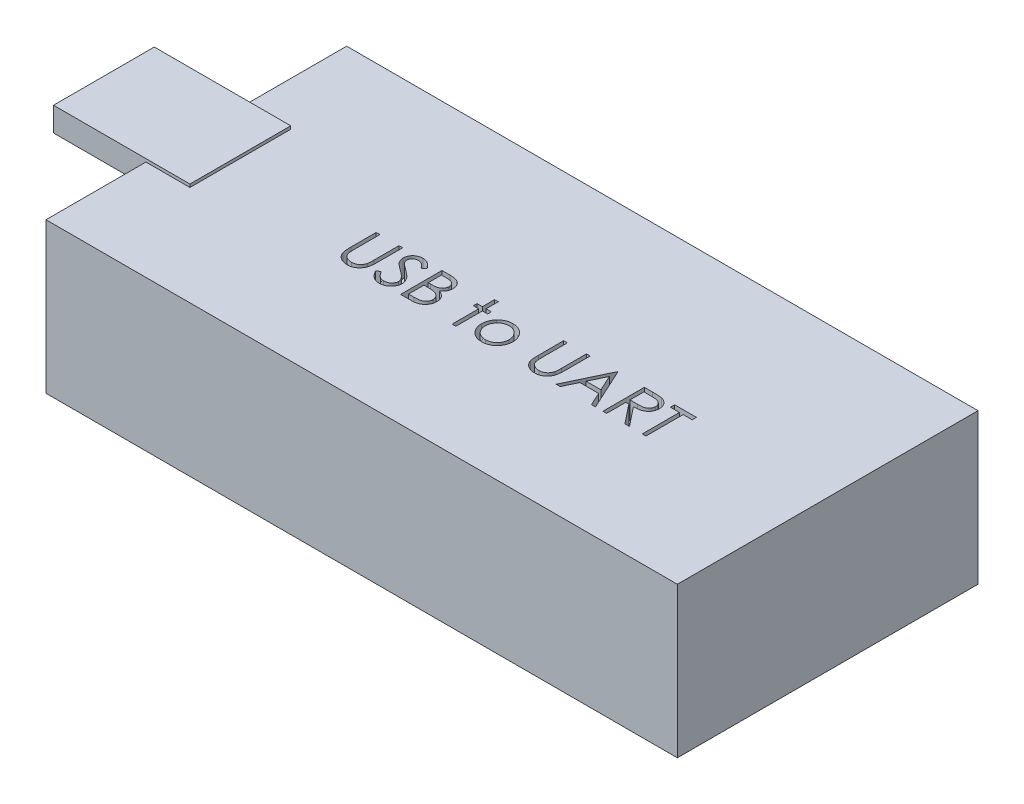
SolidWorks part; units mm, degrees
ref_plane "Front Plane" through (0, 0, 0) normal (0, 0, 1) x (1, 0, 0)
ref_plane "Top Plane" through (0, 0, 0) normal (0, 1, 0) x (1, 0, 0)
ref_plane "Right Plane" through (0, 0, 0) normal (1, 0, 0) x (0, 0, -1)
sketch "Sketch1" plane through (0, 0, 0) normal (0, 1, 0) x (1, 0, 0)
  line L0 (0, 12.7) -> (0, -12.7) construction
  line L1 (-26.67, 12.7) -> (26.67, 12.7)
  line L2 (-26.67, 12.7) -> (-26.67, -12.7)
  line L3 (-26.67, -12.7) -> (26.67, -12.7)
  line L4 (26.67, 12.7) -> (26.67, -12.7)
  line L5 (-26.67, 0) -> (26.67, 0) construction
  dimension "D1" = 53.34
  dimension "D2" = 25.4
extrude "Boss-Extrude1" add sketch "Sketch1" along normal blind 12.7 contours L2 L1 L4 L3
sketch "Sketch2" plane through (0, 12.7, 0) normal (0, 1, 0) x (1, 0, 0)
  line L0 (-26.67, 12.7) -> (-26.67, -12.7) construction
  line L1 (-26.67, -3.1822) -> (29.7809, -3.1822) construction
  text T0 "USB to UART"
extrude "Cut-Extrude1" cut sketch "Sketch2" against normal blind 1.524
sketch "Sketch7" plane through (0, 12.7, 0) normal (0, 1, 0) x (1, 0, 0)
  line L0 (0, 0) -> (-40.6122, 0) construction
  line L1 (-22.9506, 4.2581) -> (-34.4785, 4.2581)
  line L2 (-22.9506, 4.2581) -> (-22.9506, -4.2581)
  line L3 (-22.9506, -4.2581) -> (-34.4785, -4.2581)
  line L4 (-34.4785, 4.2581) -> (-34.4785, -4.2581)
  line L6 (-34.4785, 0) -> (-42.0586, 0) construction
  dimension "D1" = 8.5162
  dimension "D2" = 11.5279
extrude "Boss-Extrude4" add sketch "Sketch7" along normal blind 0.254 contours L2 L1 L4 L3
extrude "Boss-Extrude5" add sketch "Sketch7<3>" against normal blind 1.778
sketch "Sketch7<3>" plane through (0, 12.7, 0) normal (0, 1, 0) x (1, 0, 0) same geometry as "Sketch7"
sketch "Sketch9" plane through (0, 12.7, 0) normal (0, 1, 0) x (1, 0, 0)
  line L0 (-26.67, -4.2581) -> (-26.67, 4.3365) construction
